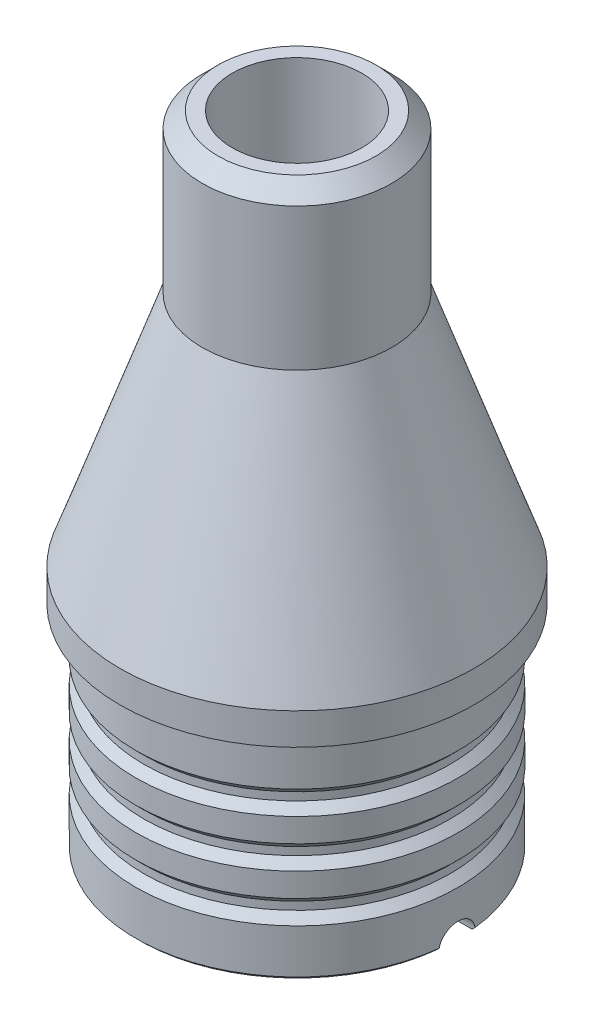
SolidWorks part; units mm, degrees
ref_plane "정면" through (0, 0, 0) normal (0, 0, 1) x (1, 0, 0)
ref_plane "윗면" through (0, 0, 0) normal (0, 1, 0) x (1, 0, 0)
ref_plane "우측면" through (0, 0, 0) normal (1, 0, 0) x (0, 0, -1)
sketch "스케치1" plane through (0, 0, 0) normal (1, 0, 0) x (0, 0, -1)
  line L0 (0, 0) -> (4.1, 0) construction
  line L1 (4.1, 0) -> (4.1, 35)
  line L2 (4.1, 35) -> (6, 35)
  line L3 (6, 35) -> (6, 25)
  line L4 (6, 25) -> (11.2, 10)
  line L5 (11.2, 10) -> (11.2, 8)
  line L6 (10.2, 0) -> (4.1, 0)
  line L7 (9.7, 5.7) -> (10.2, 5.7) construction
  line L8 (9.7, 4) -> (10.2, 4) construction
  line L9 (0, 0) -> (0, 34.546) construction
  line L10 (11.2, 8) -> (10.2, 8)
  line L11 (10.2, 8) -> (10.2, 5.7)
  line L12 (10.2, 4) -> (10.2, 0)
  line L13 (10.2, 5.7) -> (10.2, 4)
  arc A0 (9.7, 5.7) -> (9.7, 4) centre (9.7, 4.85) ccw construction
  dimension "D10" = 0.85
  dimension "D1" = 10
  dimension "D2" = 2
  dimension "D3" = 4
  dimension "D4" = 15
  dimension "D5" = 10.2
  dimension "D6" = 4.1
  dimension "D7" = 1
  dimension "D8" = 6
  dimension "D9" = 10
  dimension "D11" = 0.5
revolve "회전1" add sketch "스케치1" angle 360 about L9
chamfer "모따기1" distance 1 angle 45 1 edges at (0, 35, -6)
sketch "스케치2" plane through (0, 0, 0) normal (0, 1, 0) x (1, 0, 0)
  line L0 (0, 0) -> (0, -13.8769) construction
  line L1 (-6.3, 0) -> (0, 0) construction
  circle A0 centre (-6.3, 0) radius 1.6
  circle A1 centre (6.3, 0) radius 1.6
  dimension "D2" = 3.2
  dimension "D1" = 6.3
extrude "컷-돌출1" cut sketch "스케치2" along normal blind 3.2
sketch "스케치3" plane through (0, 0, 0) normal (0, -1, 0) x (1, 0, 0)
  circle A0 centre (0, 0) radius 10.2
  circle A1 centre (0, 0) radius 10.2 construction
  circle A2 centre (0, 0) radius 8.35
  dimension "D1" = 16.7
extrude "보스-돌출1" add sketch "스케치3" along normal blind 5.5
chamfer "모따기2" distance 0.5 angle 45 1 edges at (0, 0, -4.1)
sketch "스케치4" plane through (0, 0, 0) normal (1, 0, 0) x (0, 0, -1)
  line L0 (-10.2, -5.5) -> (10.2, -5.5) construction
  line L1 (0, 0) -> (0, -5.5) construction
  circle A0 centre (0, -5.5) radius 1.15
  dimension "D1" = 2.3
extrude "컷-돌출2" cut sketch "스케치4" against normal through all both and the other way through all
sketch "스케치6" plane through (0, 0, 0) normal (1, 0, 0) x (0, 0, -1)
  line L0 (10.2, 5) -> (9.7, 4.5)
  line L1 (10.2, -5.5) -> (10.2, 8) construction
  line L2 (9.7, 4.5) -> (9.7, 4)
  line L3 (9.7, 4) -> (10.2, 3.5)
  line L4 (10.2, 5) -> (11.2, 5)
  line L5 (11.2, 5) -> (11.2, 3.5)
  line L6 (11.2, 3.5) -> (10.2, 3.5)
  line L7 (-10.2, 8) -> (10.2, 8) construction
  line L8 (9.7, 1.5) -> (9.7, 1)
  line L9 (10.2, 2) -> (9.7, 1.5)
  line L10 (9.7, 1) -> (10.2, 0.5)
  line L11 (11.2, 0.5) -> (10.2, 0.5)
  line L12 (11.2, 2) -> (11.2, 0.5)
  line L13 (10.2, 2) -> (11.2, 2)
  line L14 (9.7, -1.5) -> (9.7, -2)
  line L15 (10.2, -1) -> (9.7, -1.5)
  line L16 (9.7, -2) -> (10.2, -2.5)
  line L17 (11.2, -2.5) -> (10.2, -2.5)
  line L18 (11.2, -1) -> (11.2, -2.5)
  line L19 (10.2, -1) -> (11.2, -1)
  dimension "D1" = 1
  dimension "D2" = 0.5
  dimension "D3" = 1.5
  dimension "D4" = 0.5
  dimension "D5" = 3
  dimension "D6" = 3
revolve "컷-회전1" cut sketch "스케치6" angle 360 about axis through (0, 0, 0) along (0, -1, 0)
chamfer "모따기3" distance 0.2 angle 45 2 edges at (0, -5.5, 10.2) (0, -5.5, -10.2)
